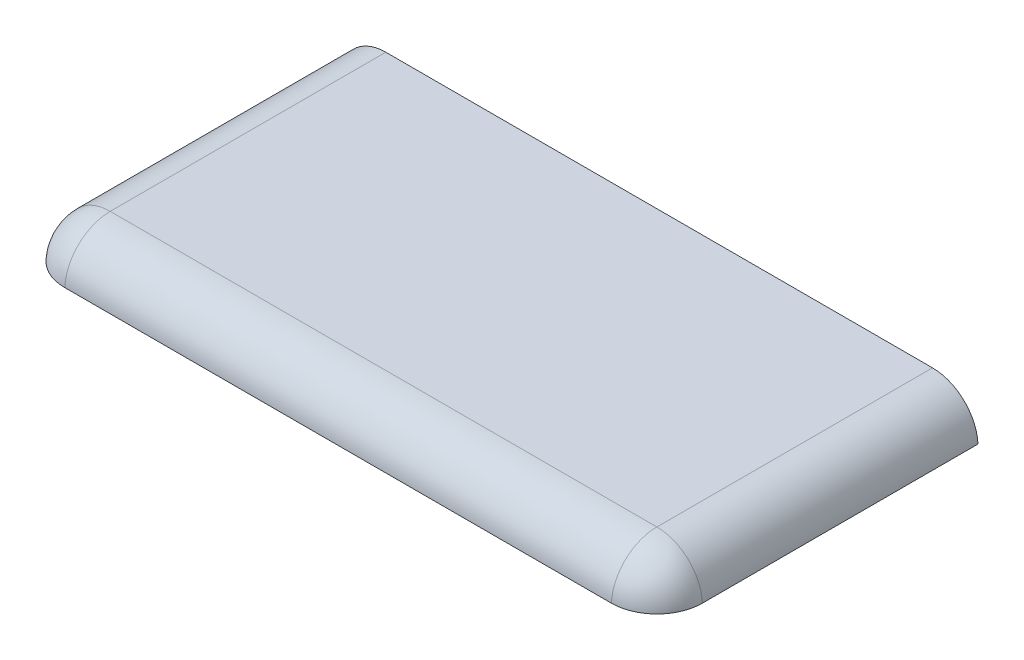
SolidWorks part; units mm, degrees
ref_plane "Front Plane" through (0, 0, 0) normal (0, 0, 1) x (1, 0, 0)
ref_plane "Top Plane" through (0, 0, 0) normal (0, 1, 0) x (1, 0, 0)
ref_plane "Right Plane" through (0, 0, 0) normal (1, 0, 0) x (0, 0, -1)
sketch "Sketch1" plane through (0, 0, 0) normal (0, 1, 0) x (1, 0, 0)
  line L1 (-60, -30) -> (60, -30)
  line L2 (-70, -20) -> (-70, 20)
  line L3 (-60, 30) -> (60, 30)
  line L4 (70, -20) -> (70, 20)
  line L5 (-70, -30) -> (70, 30) construction
  line L6 (-70, 30) -> (70, -30) construction
  arc A0 (60, 30) -> (70, 20) centre (60, 20) cw
  arc A1 (60, -30) -> (70, -20) centre (60, -20) ccw
  arc A2 (-60, -30) -> (-70, -20) centre (-60, -20) cw
  arc A3 (-70, 20) -> (-60, 30) centre (-60, 20) cw
  point P0 (0, 0)
  dimension "D3" = 10
  dimension "D1" = 60
  dimension "D2" = 140
extrude "Boss-Extrude1" add sketch "Sketch1" along normal blind 9.5
sketch "Sketch4" plane through (0, 0, -30) normal (0, 0, -1) x (-1, 0, 0)
  line L1 (-70, 9.5) -> (70, 9.5)
  line L2 (-70, 9.5) -> (-70, 0)
  line L3 (-70, 0) -> (70, 0)
  line L4 (70, 9.5) -> (70, 0)
extrude "Boss-Extrude3" add sketch "Sketch4" against normal blind 10
sketch "Sketch5" plane through (0, 0, -30) normal (0, 0, -1) x (-1, 0, 0)
  line L1 (-70, 9.5) -> (70, 9.5)
  line L2 (-70, 9.5) -> (-70, 0)
  line L3 (-70, 0) -> (70, 0)
  line L4 (70, 9.5) -> (70, 0)
extrude "Boss-Extrude4" add sketch "Sketch5" along normal blind 10.5
fillet "Fillet4" radius 10 5 edges at (-70, 9.5, -10.25) (-67.0711, 9.5, 27.0711) (0, 9.5, 30) (67.0711, 9.5, 27.0711) (70, 9.5, -10.25)
